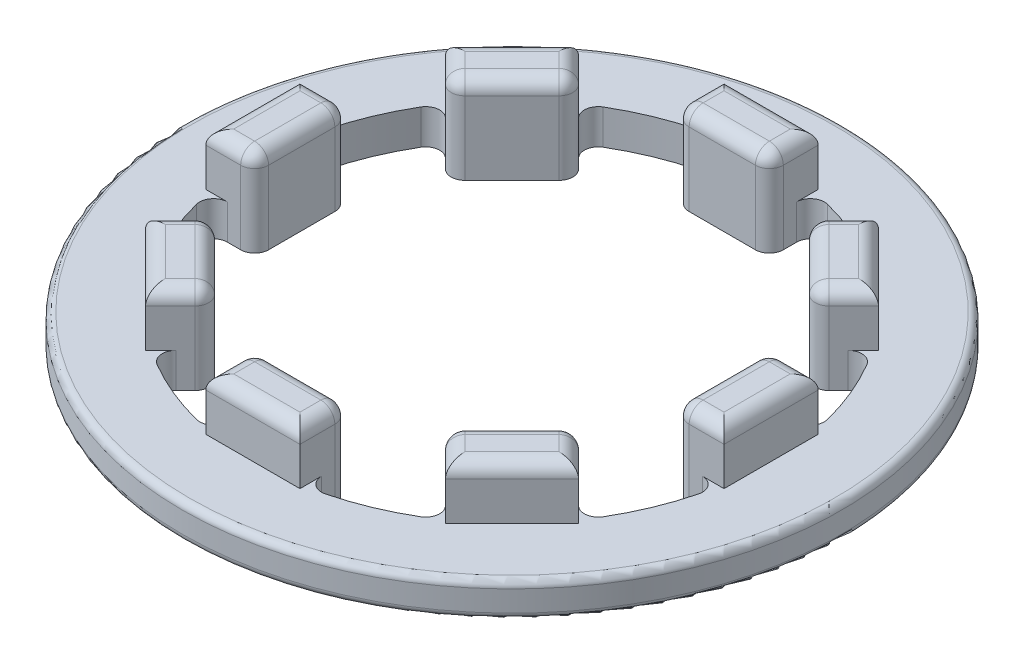
SolidWorks part; units mm, degrees
ref_plane "Front Plane" through (0, 0, 0) normal (0, 0, 1) x (1, 0, 0)
ref_plane "Top Plane" through (0, 0, 0) normal (0, 1, 0) x (1, 0, 0)
ref_plane "Right Plane" through (0, 0, 0) normal (1, 0, 0) x (0, 0, -1)
sketch "Sketch2" plane through (0, 0, 0) normal (0, 1, 0) x (1, 0, 0)
  circle A0 centre (0, 0) radius 4.725
  circle A1 centre (0, 0) radius 3.715
  dimension "D1" = 9.45
  dimension "D2" = 7.43
extrude "Boss-Extrude1" add sketch "Sketch2" along normal blind 0.5
sketch "Sketch3" plane through (0, 0, 0) normal (0, -1, 0) x (1, 0, 0)
  line L0 (0, -4.725) -> (0, 4.725) construction
  line L2 (-0.675, -3.715) -> (0.675, -3.715)
  line L3 (-0.675, -3.715) -> (-0.675, -3.015)
  line L4 (-0.675, -3.015) -> (0.675, -3.015)
  line L5 (0.675, -3.715) -> (0.675, -3.015)
  line L6 (-0.675, -3.715) -> (0.675, -3.015) construction
  line L7 (-0.675, -3.015) -> (0.675, -3.715) construction
  circle A0 centre (0, 0) radius 4.725 construction
  circle A1 centre (0, 0) radius 3.715 construction
  point P5 (0, -3.365)
  point P10 (0, -3.715)
  dimension "D1" = 1.35
  dimension "D2" = 0.7
extrude "Boss-Extrude2" add sketch "Sketch3" against normal blind 1.25
fillet "Fillet1" radius 0.2 8 edges at (0, 1.25, -3.015) (-0.675, 1.25, -3.365) (0, 1.25, -3.715) (0.675, 1.25, -3.365) (-0.675, 0.25, -3.6532) (0.675, 0.25, -3.6532) (0.675, 0.625, -3.015) (-0.675, 0.625, -3.015)
ref_axis "Axis1" through (0, 0.5, 0) along (0, -1, 0)
pattern_circular "CirPattern1" count 8 over 360 about axis through (0, 0.5, 0) along (0, -1, 0) of "Fillet1", "Boss-Extrude2"
fillet "Fillet2" radius 0.1 2 edges at (0, 0, 4.725) (0, 0.5, 4.725)
